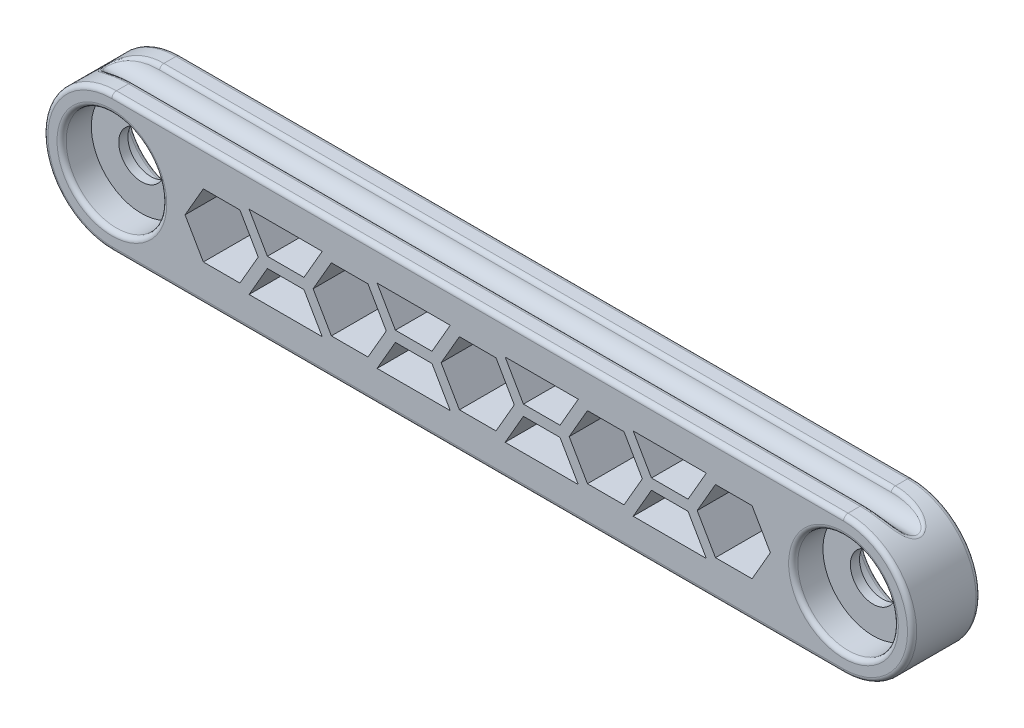
SolidWorks part; units mm, degrees
ref_plane "Front Plane" through (0, 0, 0) normal (0, 0, 1) x (1, 0, 0)
ref_plane "Top Plane" through (0, 0, 0) normal (0, 1, 0) x (1, 0, 0)
ref_plane "Right Plane" through (0, 0, 0) normal (1, 0, 0) x (0, 0, -1)
ref_axis "X" through (-88.99, 0, 0) along (1, 0, 0)
ref_axis "Y" through (0, 55, 0) along (0, -1, 0)
ref_axis "Z" through (0, 0, -88.99) along (0, 0, 1)
sketch "Sketch1" plane through (0, 0, 0) normal (0, 0, 1) x (1, 0, 0)
  line L0 (-80, 0) -> (80, 0) construction
  line L2 (-80, 15) -> (80, 15)
  line L3 (-80, -15) -> (80, -15)
  arc A0 (-80, 15) -> (-80, -15) centre (-80, 0) ccw
  arc A1 (80, -15) -> (80, 15) centre (80, 0) ccw
  circle A2 centre (80, 0) radius 11
  circle A3 centre (-80, 0) radius 11
  circle A4 centre (-80, 0) radius 5
  circle A5 centre (80, 0) radius 5
  point P5 (0, 0)
  dimension "D2" = 15
  dimension "D3" = 22
  dimension "D4" = 10
  dimension "D1" = 160
extrude "Boss-Extrude1" add sketch "Sketch1" along normal mid plane 2 contours L3 A1 L2 A0 A3 A2 | A4 A3 | A2 A5 region at (0, 0, 0) region at (69.3111, 0, 0) region at (-90.6889, 0, 0)
extrude "Boss-Extrude2" add sketch "Sketch1<3>" along normal mid plane 15 contours L3 A1 L2 A0 A3 A2 region at (0, 0, 0)
sketch "Sketch1<3>" plane through (0, 0, 0) normal (0, 0, 1) x (1, 0, 0) same geometry as "Sketch1"
sketch "Sketch2" plane through (0, 0, 0) normal (1, 0, 0) x (0, 0, -1)
  line L0 (-7.5, 15) -> (7.5, 15) construction
  line L1 (-7.5, 15) -> (7.5, 15)
  arc A0 (-3, 15) -> (3, 15) centre (0, 15) ccw
  point P6 (0, 15)
  dimension "D1" = 3
extrude "Cut-Extrude1" cut sketch "Sketch2" against normal through all both and the other way through all contours L1 A0 region at (0, 13.7268, 0)
fillet "Fillet1" radius 1 4 edges at (-88.9935, 12.0049, -0.1707) (0, 15, 3) (88.9935, 12.0049, 0.1707) (0, 15, -3)
mirror "Mirror3" [suppressed] about plane through (0, 0, 0) normal (0, 1, 0)
sketch "Sketch3" [suppressed] plane through (0, 0, 1) normal (0, 0, 1) x (1, 0, 0)
  circle A1 centre (80, 0) radius 11
  circle A2 centre (80, 0) radius 11
  circle A3 centre (80, 0) radius 5 construction
  circle A4 centre (80, 0) radius 5
  dimension "D1" = 0
extrude "Boss-Extrude3" [suppressed] add sketch "Sketch3" along normal up to surface (6.5 mm away) up to face at (91, 0, 7.5)
fillet "Fillet2" radius 1 12 edges at (-95, 0, 7.5) (0, 15, 7.5) (95, 0, 7.5) (0, -15, 7.5) (-69, 0, 7.5) (91, 0, 7.5) (95, 0, -7.5) (0, 15, -7.5) (-95, 0, -7.5) (0, -15, -7.5) (-69, 0, -7.5) (91, 0, -7.5)
mirror "Mirror1" [suppressed] about plane through (0, 0, 0) normal (1, 0, 0) of bodies 104
delete or keep bodies "Body-Delete/Keep 1" [suppressed] type keep bodies bodies 105
sketch "Sketch4" [suppressed] plane through (0, 0, 7.5) normal (0, 0, 1) x (1, 0, 0)
  circle A18 centre (87.5, 0) radius 0.75 construction
  circle A19 centre (80, -7.5) radius 0.75 construction
  circle A20 centre (72.5, 0) radius 0.75 construction
  circle A21 centre (80, 7.5) radius 0.75 construction
  circle A22 centre (87.5, 0) radius 0.75
  circle A23 centre (80, -7.5) radius 0.75
  circle A24 centre (72.5, 0) radius 0.75
  circle A25 centre (80, 7.5) radius 0.75
extrude "Cut-Extrude2" [suppressed] cut sketch "Sketch4" against normal offset from surface (6.5 mm away) 2 up to face at (85, 0, -1)
sketch "Sketch5" plane through (0, 0, 0) normal (0, 0, 1) x (1, 0, 0)
  line L0 (6, 8.0829) -> (10, 1.1547)
  line L1 (4, -6.9282) -> (8, 0)
  line L2 (8, 0) -> (4, 6.9282)
  line L3 (4, 6.9282) -> (-4, 6.9282)
  line L4 (-4, 6.9282) -> (-8, 0)
  line L5 (-8, 0) -> (-4, -6.9282)
  line L6 (-4, -6.9282) -> (4, -6.9282)
  line L7 (10, 1.1547) -> (18, 1.1547)
  line L8 (18, 1.1547) -> (22, 8.0829)
  line L9 (22, 8.0829) -> (6, 8.0829)
  line L10 (6, 3.4641) -> (8, 4.6188) construction
  line L11 (0, 0) -> (8, 0) construction
  line L12 (10, -1.1547) -> (18, -1.1547)
  line L13 (18, -1.1547) -> (22, -8.0829)
  line L14 (22, -8.0829) -> (6, -8.0829)
  line L15 (6, -8.0829) -> (10, -1.1547)
  circle A0 centre (0, 0) radius 6.9282 construction
  dimension "D1" = 8
  dimension "D2" = 2
extrude "Cut-Extrude3" cut sketch "Sketch5" against normal through all both and the other way through all contours L5 L6 L1 L2 L3 L4 region at (0, 0, 0)
extrude "Cut-Extrude4" cut sketch "Sketch5<3>" against normal through all both and the other way through all contours L15 L14 L13 L12 | L8 L9 L0 L7 region at (14, 5.0037, 0) region at (14, -5.0037, 0)
sketch "Sketch5<3>" plane through (0, 0, 0) normal (0, 0, 1) x (1, 0, 0) same geometry as "Sketch5"
pattern_linear "LPattern1" count 3 spacing 28 along (1, 0, 0) count 3 spacing 28 along (-1, 0, 0) of "Cut-Extrude3"
pattern_linear "LPattern2" count 2 spacing 28 along (1, 0, 0) count 3 spacing 28 along (-1, 0, 0) of "Cut-Extrude4"
